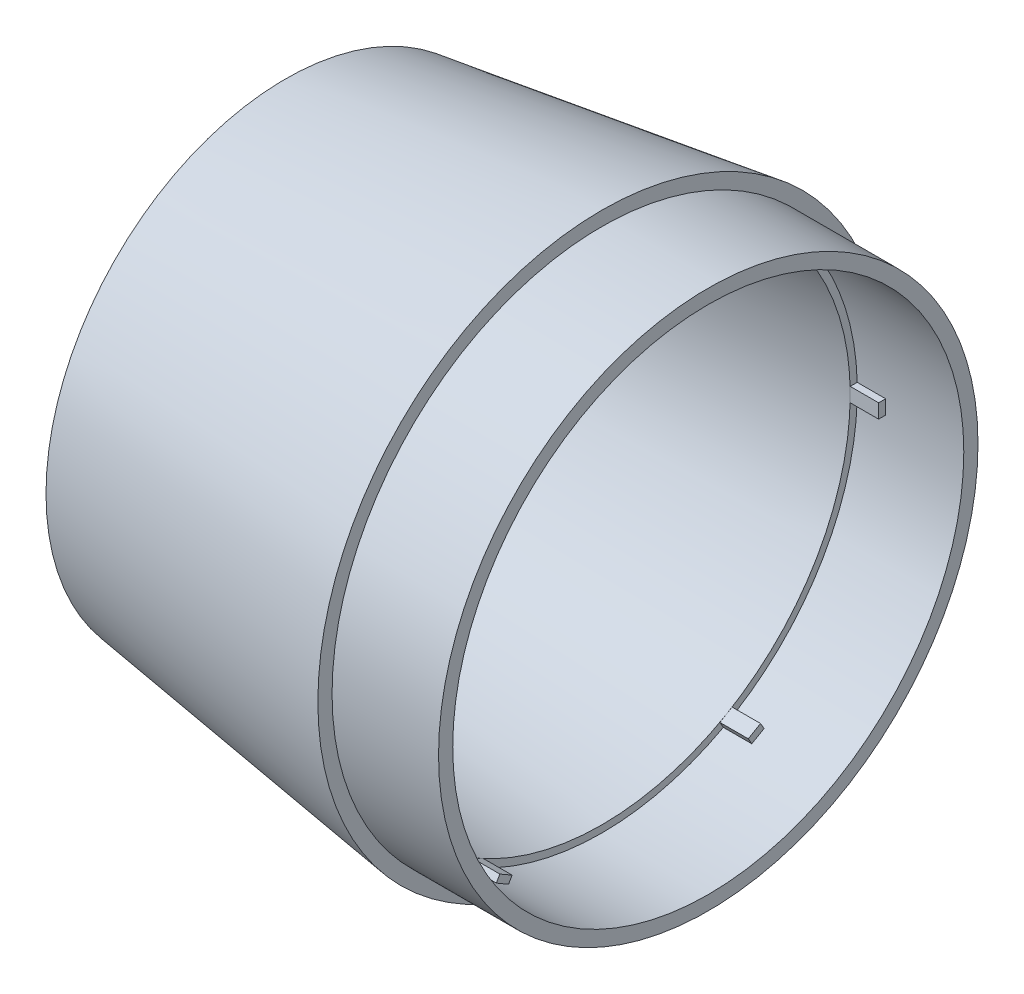
SolidWorks part; units mm, degrees
ref_plane "Ön Düzlem" through (0, 0, 0) normal (0, 0, 1) x (1, 0, 0)
ref_plane "Üst Düzlem" through (0, 0, 0) normal (0, 1, 0) x (1, 0, 0)
ref_plane "Sağ Düzlem" through (0, 0, 0) normal (1, 0, 0) x (0, 0, -1)
sketch "Çizim1" plane through (0, 0, 0) normal (0, 0, 1) x (1, 0, 0)
  line L0 (-44.5621, 33.7372) -> (-44.5621, 31.7372)
  line L1 (0, 40) -> (-44.5621, 33.7372)
  line L4 (-33.5551, 31.7372) -> (-44.5621, 31.7372)
  line L6 (15, 36) -> (15, 38)
  line L7 (-44.3163, 0) -> (0, 0)
  line L15 (0, 38) -> (15, 38)
  line L21 (0, 36) -> (15, 36)
  line L23 (0, 40) -> (0, 38)
  line L25 (-33.5551, 31.7372) -> (0, 35)
  line L26 (0, 36) -> (0, 35)
  dimension "D1" = 2
  dimension "D2" = 44.3163
ref_axis "Eksen1" through (0, 0, 0) along (-1, 0, 0)
revolve "Döndür2" add sketch "Çizim1" angle 360 about L7 region at (-15.7963, 35.4536, 0)
sketch "Çizim3" plane through (0, 0, 0) normal (0, 1, 0) x (1, 0, 0)
  line L0 (0, -36) -> (15, -36) construction
  line L4 (0, -36) -> (4, -36)
  line L6 (4, -36) -> (4, -35)
  line L7 (4, -35) -> (0, -35)
  line L9 (0, -35) -> (0, -36)
  dimension "D1" = 4
extrude "Yükseklik-Ekstrüzyon1" add sketch "Çizim3" along normal blind 1 and the other way blind 1
pattern_circular "Dairesel Kaplama1" count 6 over 360 about axis through (0, 0, 0) along (-1, 0, 0) of "Yükseklik-Ekstrüzyon1"
